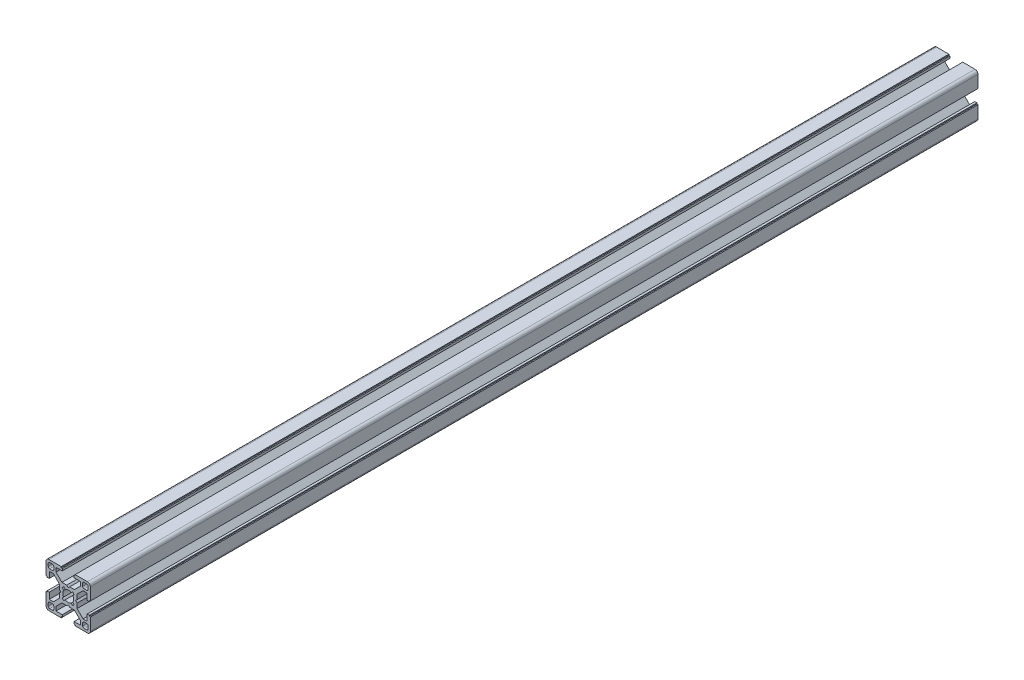
SolidWorks part; units mm, degrees
material "6063-O, Barra estrusa (SS)"
ref_plane "Piano frontale" through (0, 0, 0) normal (0, 0, 1) x (1, 0, 0)
ref_plane "Piano superiore" through (0, 0, 0) normal (0, 1, 0) x (1, 0, 0)
ref_plane "Piano destro" through (0, 0, 0) normal (1, 0, 0) x (0, 0, -1)
sketch "Schizzo1" plane through (0, 0, 0) normal (0, 0, 1) x (1, 0, 0)
  line L0 (-125.0647, 0) -> (53.776, 0) construction
  line L1 (0, -44.8297) -> (0, 95.2781) construction
  line L2 (-15, 13) -> (-15, 4.7)
  line L3 (-15, 4.7) -> (-14.3, 4.7)
  line L4 (-14.3, 4.7) -> (-14.3, 4)
  line L5 (-14.3, 4) -> (-12.8, 4)
  line L6 (-12.8, 4) -> (-12.8, 8.25)
  line L7 (-12.8, 8.25) -> (-10.0178, 8.25)
  line L8 (-10.0178, 8.25) -> (-6, 4.2322)
  line L9 (-6, 4.2322) -> (-6, 1)
  line L10 (-6, 1) -> (-5, 0)
  line L11 (-1, 6) -> (0, 5)
  line L12 (0, 0) -> (-161.3113, 161.3113) construction
  line L13 (-4.2322, 6) -> (-1, 6)
  line L14 (-8.25, 10.0178) -> (-4.2322, 6)
  line L15 (-8.25, 12.8) -> (-8.25, 10.0178)
  line L16 (-4, 12.8) -> (-8.25, 12.8)
  line L17 (-4, 14.3) -> (-4, 12.8)
  line L18 (-4.7, 14.3) -> (-4, 14.3)
  line L19 (-4.7, 15) -> (-4.7, 14.3)
  line L20 (-13, 15) -> (-4.7, 15)
  line L21 (13.5, 10.75) -> (13.5, 12.5)
  line L22 (10.75, 13.5) -> (12.5, 13.5)
  line L23 (9.75, 10.75) -> (9.75, 12.5)
  line L24 (10.75, 9.75) -> (12.5, 9.75)
  line L25 (10.75, -13.5) -> (12.5, -13.5)
  line L26 (13.5, -10.75) -> (13.5, -12.5)
  line L27 (10.75, -9.75) -> (12.5, -9.75)
  line L28 (9.75, -10.75) -> (9.75, -12.5)
  line L29 (-13.5, -10.75) -> (-13.5, -12.5)
  line L30 (-10.75, -13.5) -> (-12.5, -13.5)
  line L31 (-9.75, -10.75) -> (-9.75, -12.5)
  line L32 (-10.75, -9.75) -> (-12.5, -9.75)
  line L33 (1.9955, 3.0562) -> (3.0052, 4.0659)
  line L34 (3.0052, 4.0659) -> (4.0659, 3.0052)
  line L35 (4.0659, 3.0052) -> (3.0562, 1.9955)
  line L36 (3.0562, -1.9955) -> (4.0659, -3.0052)
  line L37 (4.0659, -3.0052) -> (3.0052, -4.0659)
  line L38 (3.0052, -4.0659) -> (1.9955, -3.0562)
  line L39 (-1.9955, -3.0562) -> (-3.0052, -4.0659)
  line L40 (-3.0052, -4.0659) -> (-4.0659, -3.0052)
  line L41 (-4.0659, -3.0052) -> (-3.0562, -1.9955)
  line L42 (1, 6) -> (0, 5)
  line L43 (4.2322, 6) -> (1, 6)
  line L44 (8.25, 10.0178) -> (4.2322, 6)
  line L45 (8.25, 12.8) -> (8.25, 10.0178)
  line L46 (4, 12.8) -> (8.25, 12.8)
  line L47 (12.8, 4) -> (12.8, 8.25)
  line L48 (12.8, 8.25) -> (10.0178, 8.25)
  line L49 (10.0178, 8.25) -> (6, 4.2322)
  line L50 (6, 4.2322) -> (6, 1)
  line L51 (6, 1) -> (5, 0)
  line L52 (6, -1) -> (5, 0)
  line L53 (6, -4.2322) -> (6, -1)
  line L54 (10.0178, -8.25) -> (6, -4.2322)
  line L55 (12.8, -8.25) -> (10.0178, -8.25)
  line L56 (12.8, -4) -> (12.8, -8.25)
  line L57 (4, -12.8) -> (8.25, -12.8)
  line L58 (8.25, -12.8) -> (8.25, -10.0178)
  line L59 (8.25, -10.0178) -> (4.2322, -6)
  line L60 (4.2322, -6) -> (1, -6)
  line L61 (1, -6) -> (0, -5)
  line L62 (-1, -6) -> (0, -5)
  line L63 (-4.2322, -6) -> (-1, -6)
  line L64 (-8.25, -10.0178) -> (-4.2322, -6)
  line L65 (-8.25, -12.8) -> (-8.25, -10.0178)
  line L66 (-4, -12.8) -> (-8.25, -12.8)
  line L67 (-12.8, -4) -> (-12.8, -8.25)
  line L68 (-12.8, -8.25) -> (-10.0178, -8.25)
  line L69 (-10.0178, -8.25) -> (-6, -4.2322)
  line L70 (-6, -4.2322) -> (-6, -1)
  line L71 (-6, -1) -> (-5, 0)
  line L72 (4, 14.3) -> (4, 12.8)
  line L73 (4.7, 14.3) -> (4, 14.3)
  line L74 (4.7, 15) -> (4.7, 14.3)
  line L75 (-3.0562, 1.9955) -> (-4.0659, 3.0052)
  line L76 (-4.0659, 3.0052) -> (-3.0052, 4.0659)
  line L77 (-3.0052, 4.0659) -> (-1.9955, 3.0562)
  line L78 (15, 4.7) -> (14.3, 4.7)
  line L79 (-10.75, 9.75) -> (-12.5, 9.75)
  line L80 (-9.75, 10.75) -> (-9.75, 12.5)
  line L81 (-10.75, 13.5) -> (-12.5, 13.5)
  line L82 (-13.5, 10.75) -> (-13.5, 12.5)
  line L83 (14.3, 4.7) -> (14.3, 4)
  line L84 (14.3, 4) -> (12.8, 4)
  line L85 (14.3, -4) -> (12.8, -4)
  line L86 (14.3, -4.7) -> (14.3, -4)
  line L87 (15, -4.7) -> (14.3, -4.7)
  line L88 (4.7, -15) -> (4.7, -14.3)
  line L89 (4.7, -14.3) -> (4, -14.3)
  line L90 (4, -14.3) -> (4, -12.8)
  line L91 (-4, -14.3) -> (-4, -12.8)
  line L92 (-4.7, -14.3) -> (-4, -14.3)
  line L93 (-4.7, -15) -> (-4.7, -14.3)
  line L94 (-15, -4.7) -> (-14.3, -4.7)
  line L95 (-14.3, -4.7) -> (-14.3, -4)
  line L96 (-14.3, -4) -> (-12.8, -4)
  line L97 (4, 14.3) -> (4, 12.8)
  line L98 (4.7, 14.3) -> (4, 14.3)
  line L99 (4.7, 15) -> (4.7, 14.3)
  line L100 (15, 4.7) -> (14.3, 4.7)
  line L101 (14.3, 4.7) -> (14.3, 4)
  line L102 (14.3, 4) -> (12.8, 4)
  line L103 (13, 15) -> (4.7, 15)
  line L104 (15, 13) -> (15, 4.7)
  line L105 (14.3, -4) -> (12.8, -4)
  line L106 (14.3, -4.7) -> (14.3, -4)
  line L107 (15, -4.7) -> (14.3, -4.7)
  line L108 (4.7, -15) -> (4.7, -14.3)
  line L109 (4.7, -14.3) -> (4, -14.3)
  line L110 (4, -14.3) -> (4, -12.8)
  line L111 (15, -13) -> (15, -4.7)
  line L112 (13, -15) -> (4.7, -15)
  line L113 (-4, -14.3) -> (-4, -12.8)
  line L114 (-4.7, -14.3) -> (-4, -14.3)
  line L115 (-4.7, -15) -> (-4.7, -14.3)
  line L116 (-15, -4.7) -> (-14.3, -4.7)
  line L117 (-14.3, -4.7) -> (-14.3, -4)
  line L118 (-14.3, -4) -> (-12.8, -4)
  line L119 (-13, -15) -> (-4.7, -15)
  line L120 (-15, -13) -> (-15, -4.7)
  arc A0 (-3.65, 0) -> (-3.0562, 1.9955) centre (0, 0) cw
  arc A1 (-1.9955, 3.0562) -> (0, 3.65) centre (0, 0) cw
  arc A2 (-13, 15) -> (-15, 13) centre (-13, 13) ccw
  arc A3 (-13.5, 10.75) -> (-12.5, 9.75) centre (-12.5, 10.75) ccw
  arc A4 (-9.75, 10.75) -> (-10.75, 9.75) centre (-10.75, 10.75) cw
  arc A5 (-10.75, 13.5) -> (-9.75, 12.5) centre (-10.75, 12.5) cw
  arc A6 (-12.5, 13.5) -> (-13.5, 12.5) centre (-12.5, 12.5) ccw
  arc A7 (13.5, 12.5) -> (12.5, 13.5) centre (12.5, 12.5) ccw
  arc A8 (13.5, 10.75) -> (12.5, 9.75) centre (12.5, 10.75) cw
  arc A9 (10.75, 9.75) -> (9.75, 10.75) centre (10.75, 10.75) cw
  arc A10 (10.75, 13.5) -> (9.75, 12.5) centre (10.75, 12.5) ccw
  arc A11 (12.5, -13.5) -> (13.5, -12.5) centre (12.5, -12.5) ccw
  arc A12 (10.75, -13.5) -> (9.75, -12.5) centre (10.75, -12.5) cw
  arc A13 (9.75, -10.75) -> (10.75, -9.75) centre (10.75, -10.75) cw
  arc A14 (13.5, -10.75) -> (12.5, -9.75) centre (12.5, -10.75) ccw
  arc A15 (-13.5, -12.5) -> (-12.5, -13.5) centre (-12.5, -12.5) ccw
  arc A16 (-13.5, -10.75) -> (-12.5, -9.75) centre (-12.5, -10.75) cw
  arc A17 (-10.75, -9.75) -> (-9.75, -10.75) centre (-10.75, -10.75) cw
  arc A18 (-10.75, -13.5) -> (-9.75, -12.5) centre (-10.75, -12.5) ccw
  arc A19 (0, 3.65) -> (1.9955, 3.0562) centre (0, 0) cw
  arc A20 (3.0562, 1.9955) -> (3.65, 0) centre (0, 0) cw
  arc A21 (3.65, 0) -> (3.0562, -1.9955) centre (0, 0) cw
  arc A22 (1.9955, -3.0562) -> (0, -3.65) centre (0, 0) cw
  arc A23 (0, -3.65) -> (-1.9955, -3.0562) centre (0, 0) cw
  arc A24 (-3.0562, -1.9955) -> (-3.65, 0) centre (0, 0) cw
  arc A25 (15, 13) -> (13, 15) centre (13, 13) ccw
  arc A26 (13, -15) -> (15, -13) centre (13, -13) ccw
  arc A27 (-15, -13) -> (-13, -15) centre (-13, -13) ccw
  point P70 (0, 0)
  point P86 (0, 0)
  point P88 (-15, 15)
  point P100 (-9.75, 9.75)
  point P107 (0, 0)
  point P144 (0, 0)
  point P169 (0, 0)
  point P197 (0, 0)
  dimension "D11" = 7.3
  dimension "D14" = 2
  dimension "D17" = 1
  dimension "D1" = 45
  dimension "D2" = 8
  dimension "D3" = 16.5
  dimension "D4" = 9
  dimension "D5" = 2.2
  dimension "D6" = 15
  dimension "D7" = 2.5
  dimension "D8" = 8.3
  dimension "D9" = 2
  dimension "D12" = 5
  dimension "D13" = 1.5
  dimension "D15" = 1.5
  dimension "D16" = 1.5
  dimension "D10" = 4
  dimension "D18" = 4
  dimension "D19" = 4
  dimension "D20" = 4
  dimension "D21" = 4
extrude "Estrusione-Estrusione2" add sketch "Schizzo1" along normal blind 600 contours L120 A27 L119 L93 L92 L91 L66 L65 L64 L63 L62 L61 L60 L59 L58 L57 L90 L89 L88 L112 A26 L111 L87 L86 L85 L56 L55 L54 L53 L52 L51 L50 L49 L48 L47 L84 L83 L78 L104 A25 L103 L74 L73 L72 L46 L45 L44 L43 L42 L11 L13 region at (-14.1142, 14.1142, 0)
